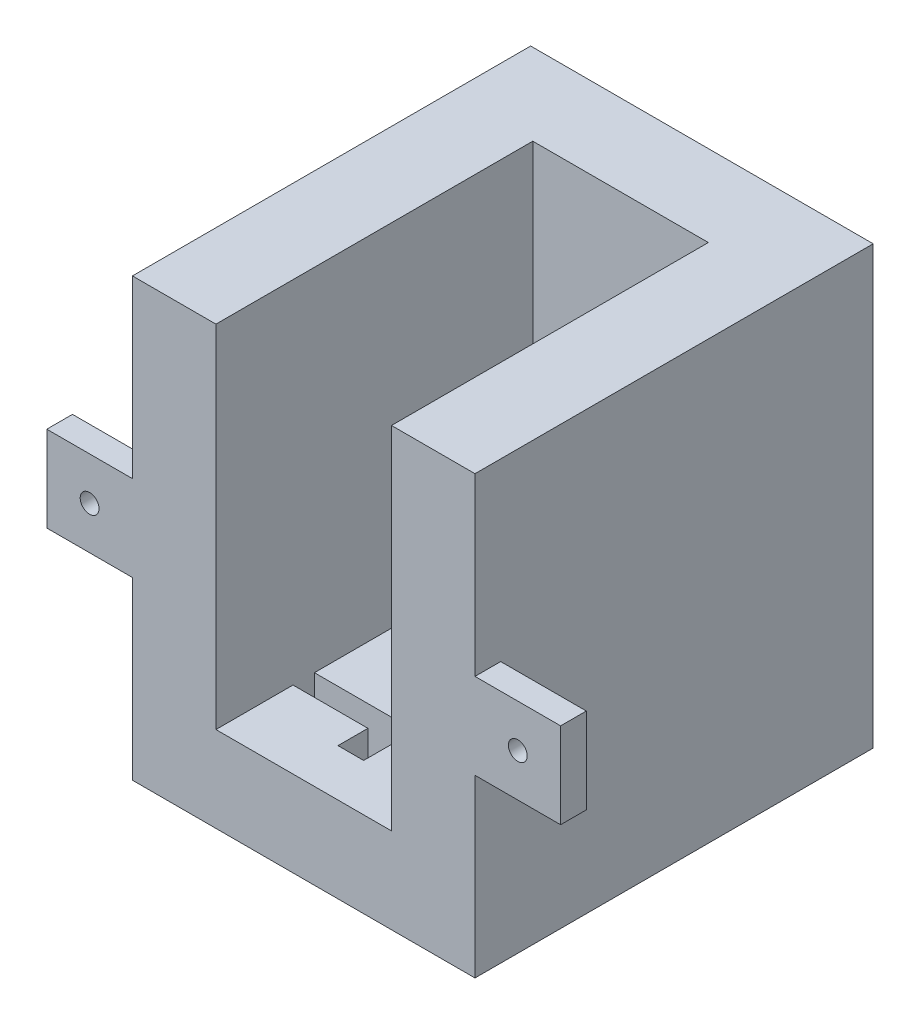
SolidWorks part; units mm, degrees
ref_plane "Front Plane" through (0, 0, 0) normal (0, 0, 1) x (1, 0, 0)
ref_plane "Top Plane" through (0, 0, 0) normal (0, 1, 0) x (1, 0, 0)
ref_plane "Right Plane" through (0, 0, 0) normal (1, 0, 0) x (0, 0, -1)
sketch "Sketch1" plane through (0, 0, 0) normal (0, 1, 0) x (1, 0, 0)
  line L1 (-20, -23.25) -> (20, -23.25)
  line L2 (-20, -23.25) -> (-20, 23.25)
  line L3 (-20, 23.25) -> (20, 23.25)
  line L4 (20, -23.25) -> (20, 23.25)
  line L5 (-20, -23.25) -> (20, 23.25) construction
  line L6 (-20, 23.25) -> (20, -23.25) construction
  point P0 (0, 0)
  dimension "D1" = 46.5
  dimension "D2" = 40
extrude "Boss-Extrude1" add sketch "Sketch1" along normal blind 51
sketch "Sketch2" plane through (0, 51, 0) normal (0, 1, 0) x (1, 0, 0)
  line L0 (-20, -23.25) -> (20, -23.25) construction
  line L1 (-10.25, 13.75) -> (10.25, 13.75)
  line L2 (-10.25, 13.75) -> (-10.25, -23.25)
  line L3 (-10.25, -23.25) -> (10.25, -23.25)
  line L4 (10.25, 13.75) -> (10.25, -23.25)
  line L5 (20, -23.25) -> (20, 23.25) construction
  line L6 (-20, 23.25) -> (-20, -23.25) construction
  line L7 (20, 23.25) -> (-20, 23.25) construction
  dimension "D1" = 9.75
  dimension "D2" = 9.75
  dimension "D3" = 9.5
extrude "Cut-Extrude1" cut sketch "Sketch2" against normal blind 41
sketch "Sketch3" plane through (0, 10, 0) normal (0, 1, 0) x (1, 0, 0)
  line L0 (-10.25, 13.75) -> (-10.25, -23.25) construction
  line L1 (-10.25, -11.75) -> (10.25, -11.75)
  line L2 (-10.25, -11.75) -> (-10.25, -14.25)
  line L3 (-10.25, -14.25) -> (-1.5, -14.25)
  line L4 (10.25, -11.75) -> (10.25, -14.25)
  line L5 (10.25, -23.25) -> (10.25, 13.75) construction
  line L6 (10.25, 13.75) -> (-10.25, 13.75) construction
  line L7 (1.5, -14.25) -> (10.25, -14.25)
  line L9 (-1.5, -14.25) -> (-1.5, -17.75)
  line L10 (-1.5, -17.75) -> (1.5, -17.75)
  line L11 (1.5, -14.25) -> (1.5, -17.75)
  dimension "D1" = 25.5
  dimension "D2" = 2.5
  dimension "D3" = 3
  dimension "D4" = 3.5
  dimension "D5" = 8.75
extrude "Cut-Extrude2" cut sketch "Sketch3" against normal blind 8.5 contours L7 L4 L1 L2 L3 L9 L10 L11
sketch "Sketch4" plane through (20, 0, 0) normal (1, 0, 0) x (0, 0, -1)
  line L0 (-23.25, 51) -> (-23.25, 0) construction
  line L1 (-20.25, 30.5) -> (-23.25, 30.5)
  line L2 (-20.25, 30.5) -> (-20.25, 20.5)
  line L3 (-20.25, 20.5) -> (-23.25, 20.5)
  line L4 (-23.25, 30.5) -> (-23.25, 20.5)
  line L5 (-23.25, 0) -> (23.25, 0) construction
  dimension "D1" = 3
  dimension "D2" = 10
  dimension "D3" = 20.5
extrude "Boss-Extrude2" add sketch "Sketch4" along normal blind 10
sketch "Sketch5" plane through (0, 0, 20.25) normal (0, 0, -1) x (-1, 0, 0)
  line L0 (-30, 20.5) -> (-20, 20.5) construction
  line L1 (-20, 20.5) -> (-20, 30.5) construction
  circle A0 centre (-25, 25.5) radius 1.1
  point P2 (0, 0)
  point P5 (0, 0)
  dimension "D1" = 2.2
  dimension "D2" = 5
  dimension "D3" = 5
extrude "Cut-Extrude3" cut sketch "Sketch5" against normal blind 10
sketch "Sketch6" plane through (-20, 0, 0) normal (-1, 0, 0) x (0, 0, 1)
  line L0 (23.25, 51) -> (23.25, 0) construction
  line L1 (23.25, 20.5) -> (20.25, 20.5)
  line L2 (23.25, 20.5) -> (23.25, 30.5)
  line L3 (23.25, 30.5) -> (20.25, 30.5)
  line L4 (20.25, 20.5) -> (20.25, 30.5)
  line L5 (-23.25, 0) -> (23.25, 0) construction
  dimension "D1" = 3
  dimension "D2" = 10
  dimension "D3" = 20.5
extrude "Boss-Extrude3" add sketch "Sketch6" along normal blind 10
sketch "Sketch7" plane through (0, 0, 20.25) normal (0, 0, -1) x (-1, 0, 0)
  line L0 (30, 20.5) -> (20, 20.5) construction
  line L1 (30, 30.5) -> (30, 20.5) construction
  circle A0 centre (25, 25.5) radius 1.1
  dimension "D1" = 2.2
  dimension "D2" = 5
  dimension "D3" = 5
extrude "Cut-Extrude4" cut sketch "Sketch7" against normal blind 10
